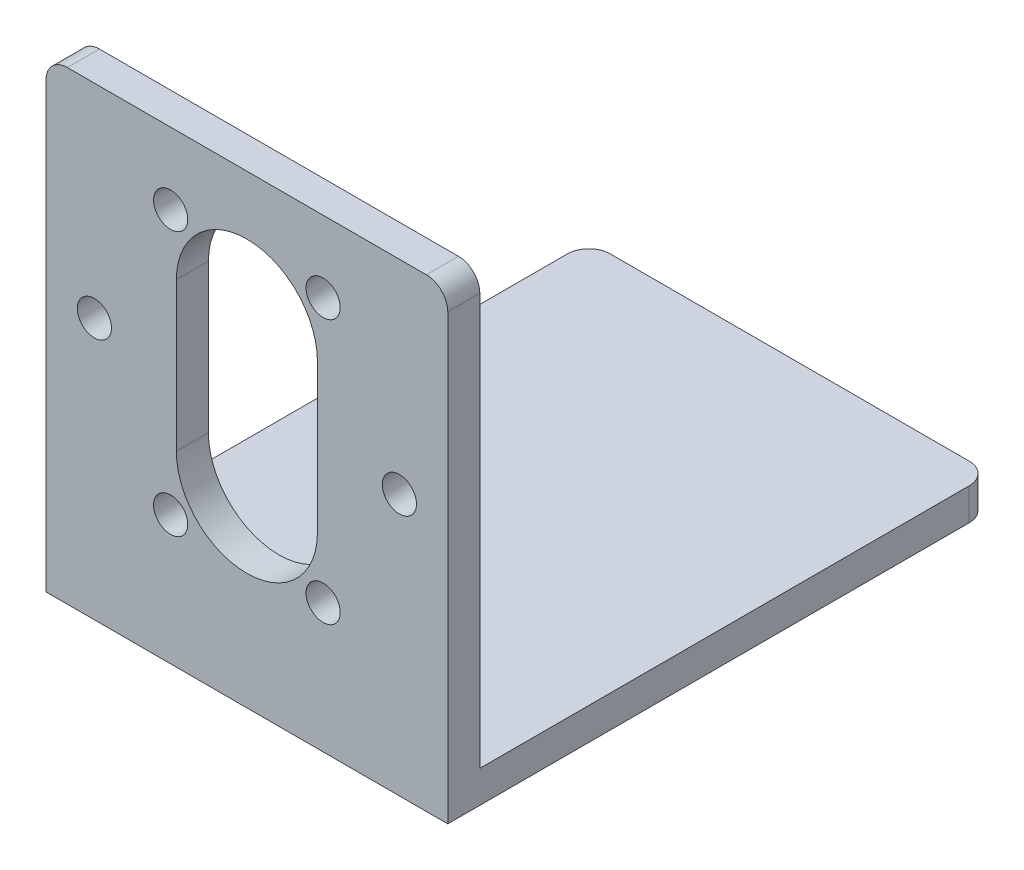
SolidWorks part; units mm, degrees
ref_plane "Front Plane" through (0, 0, 0) normal (0, 0, 1) x (1, 0, 0)
ref_plane "Top Plane" through (0, 0, 0) normal (0, 1, 0) x (1, 0, 0)
ref_plane "Right Plane" through (0, 0, 0) normal (1, 0, 0) x (0, 0, -1)
sketch "Sketch1" plane through (0, 0, 0) normal (0, 0, 1) x (1, 0, 0)
  line L0 (0, 0) -> (0, 42) construction
  line L1 (-18.8, 0) -> (18.8, 0)
  line L2 (-18.8, 0) -> (-18.8, 22)
  line L3 (-18.8, 22) -> (-18.8, 42)
  line L4 (18.8, 0) -> (18.8, 22)
  line L5 (-18.8, 42) -> (18.8, 42)
  line L6 (-6.6, 16) -> (-6.6, 29.9)
  line L7 (18.8, 42) -> (18.8, 22)
  line L8 (6.6, 16) -> (6.6, 29.9)
  arc A1 (-6.6, 29.9) -> (6.6, 29.9) centre (0, 29.9) cw
  arc A2 (-6.6, 16) -> (6.6, 16) centre (0, 16) ccw
  point P4 (0, 36.5)
  point P15 (0, 22.95)
  dimension "D3" = 5.5
  dimension "D5" = 27.1
  dimension "D6" = 42
  dimension "D1" = 37.6
  dimension "D2" = 22
  dimension "D4" = 13.2
  dimension "D7" = 13.9
  dimension "D8" = 6.95
extrude "Boss-Extrude1" add sketch "Sketch1" along normal blind 3
sketch "Sketch2" plane through (0, 0, 0) normal (0, -1, 0) x (1, 0, 0)
  line L0 (18.8, 3) -> (18.8, 0) construction
  line L1 (-18.8, 3) -> (18.8, 3)
  line L2 (-18.8, 3) -> (-18.8, -47.8)
  line L3 (-18.8, -47.8) -> (18.8, -47.8)
  line L4 (18.8, 3) -> (18.8, -47.8)
  dimension "D1" = 50.8
extrude "Boss-Extrude2" add sketch "Sketch2" against normal blind 1.5 and the other way blind 1.5
fillet "Fillet2" radius 2 4 edges at (-18.8, 0, -47.8) (18.8, 0, -47.8) (-18.8, 42, 1.5) (18.8, 42, 1.5)
sketch "Sketch4" plane through (0, 0, 3) normal (0, 0, 1) x (1, 0, 0)
  line L0 (0, 0) -> (0, 39.6) construction
  line L1 (-7.1354, 35.3089) -> (-5.815, 33.0218) construction
  line L2 (-5.815, 33.0218) -> (0, 22.95) construction
  line L3 (0, 22.95) -> (-5.815, 12.8782) construction
  line L4 (0, 22.95) -> (5.815, 12.8782) construction
  line L5 (5.815, 12.8782) -> (7.1354, 10.5911) construction
  line L6 (0, 22.95) -> (5.815, 33.0218) construction
  line L7 (5.815, 33.0218) -> (7.1354, 35.3089) construction
  line L8 (-5.815, 12.8782) -> (-7.1354, 10.5911) construction
  line L9 (7.325, 33.2258) -> (7.1354, 35.3089) construction
  line L10 (7.1354, 35.3089) -> (8.4558, 37.5959) construction
  circle A0 centre (7.1354, 35.3089) radius 1.6
  arc A1 (18.8, 22) -> (-18.8, 22) centre (0, 20.7591) ccw construction
  circle A3 centre (14.2708, 22.95) radius 1.6
  circle A4 centre (7.1354, 10.5911) radius 1.6
  circle A5 centre (-7.1354, 10.5911) radius 1.6
  circle A6 centre (-14.2708, 22.95) radius 1.6
  circle A7 centre (-7.1354, 35.3089) radius 1.6
  arc A8 (-6.6, 16) -> (6.6, 16) centre (0, 16) ccw construction
  arc A9 (6.6, 29.9) -> (-6.6, 29.9) centre (0, 29.9) ccw construction
  point P26 (0, 22.95)
  dimension "D1" = 3.2
  dimension "D2" = 6
extrude "Cut-Extrude2" cut sketch "Sketch4" against normal up to next
sketch "Szkic1" plane through (0, 1.5, 0) normal (0, 1, 0) x (1, 0, 0)
  line L0 (18.8, 0) -> (-18.8, 0) construction
  circle A0 centre (0, 15) radius 2.5
  circle A1 centre (0, 35) radius 2.5
  dimension "D1" = 5
  dimension "D2" = 5
  dimension "D3" = 20
  dimension "D4" = 15
sketch "Szkic2" plane through (0, 1.5, 0) normal (0, 1, 0) x (1, 0, 0)
  line L0 (-16.8, 47.8) -> (16.8, 47.8) construction
  line L1 (18.8, 0) -> (18.8, 47.8)
  line L2 (18.8, 47.8) -> (-18.8, 47.8)
  line L3 (-18.8, 0) -> (-18.8, 47.8)
  ellipse E0 centre (0, -45.5597) end of major axis (0, -138.9194) minor radius 21.5388 (18.8, 0) -> (-18.8, 0) ccw
